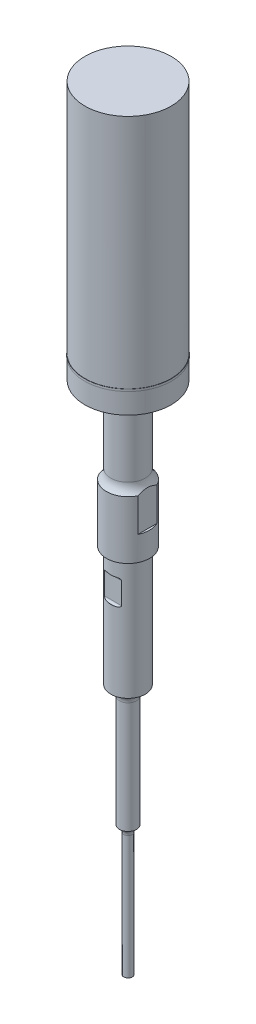
SolidWorks part; units mm, degrees
ref_plane "Front Plane" through (0, 0, 0) normal (0, 0, 1) x (1, 0, 0)
ref_plane "Top Plane" through (0, 0, 0) normal (0, 1, 0) x (1, 0, 0)
ref_plane "Right Plane" through (0, 0, 0) normal (1, 0, 0) x (0, 0, -1)
sketch "Sketch1" plane through (0, 0, 0) normal (0, 0, 1) x (1, 0, 0)
  line L0 (0, 0) -> (15.875, 0)
  line L1 (15.875, 0) -> (15.875, -95.25)
  line L2 (15.875, -95.25) -> (7.75, -95.25)
  line L3 (6.35, -99.25) -> (6.35, -123.35)
  line L5 (7.9375, -126.85) -> (7.9375, -148.15)
  line L6 (7.9375, -148.15) -> (6.35, -148.15)
  line L7 (6.35, -148.15) -> (6.35, -192.25)
  line L9 (3.15, -195.95) -> (3.15, -236.95)
  line L11 (1.6, -239.35) -> (1.6, -284.75)
  line L12 (1.6, -284.75) -> (0, -284.75)
  line L13 (0, -284.75) -> (0, 0)
  line L14 (-1.6, -239.35) -> (-1.6, -284.75) construction
  line L16 (-3.15, -195.95) -> (-3.15, -236.95) construction
  line L18 (-6.35, -148.15) -> (-6.35, -192.25) construction
  line L19 (-7.9375, -148.15) -> (-6.35, -148.15) construction
  line L20 (-7.9375, -126.85) -> (-7.9375, -148.15) construction
  line L22 (-6.35, -99.25) -> (-6.35, -123.35) construction
  line L23 (-15.875, -95.25) -> (-7.75, -95.25) construction
  line L24 (-15.875, 0) -> (-15.875, -95.25) construction
  arc A0 (6.35, -99.25) -> (7.75, -95.25) centre (12.7643, -99.25) cw
  arc A1 (-6.35, -99.25) -> (-7.75, -95.25) centre (-12.7643, -99.25) ccw construction
  arc A2 (6.35, -123.35) -> (7.9375, -126.85) centre (11.002, -123.35) ccw
  arc A3 (-6.35, -123.35) -> (-7.9375, -126.85) centre (-11.002, -123.35) cw construction
  arc A4 (1.6, -239.35) -> (3.15, -236.95) centre (4.2331, -239.35) cw
  arc A5 (-1.6, -239.35) -> (-3.15, -236.95) centre (-4.2331, -239.35) ccw construction
  arc A6 (3.15, -195.95) -> (6.35, -192.25) centre (6.8891, -195.95) cw
  arc A7 (-3.15, -195.95) -> (-6.35, -192.25) centre (-6.8891, -195.95) ccw construction
  dimension "D1" = 31.75
  dimension "D2" = 95.25
  dimension "D3" = 12.7
  dimension "D4" = 21.3
  dimension "D5" = 31.6
  dimension "D6" = 44.1
  dimension "D7" = 44.7
  dimension "D8" = 47.8
  dimension "D9" = 3.2
  dimension "D10" = 6.3
  dimension "D11" = 12.7
  dimension "D12" = 15.875
  dimension "D13" = 4
  dimension "D14" = 15.5
  dimension "D15" = 3.5
  dimension "D16" = 2.4
  dimension "D17" = 3.7
revolve "Revolve1" add sketch "Sketch1" angle 360 about L13
sketch "Sketch3" plane through (0, 0, 0) normal (0, 0, 1) x (1, 0, 0)
  line L0 (-7.9375, -126.85) -> (-7.9375, -148.15)
  line L1 (7.9375, -148.15) -> (7.9375, -126.85)
  line L2 (7.9375, -139.15) -> (7.9375, -126.85)
  line L3 (0, -17.4625) -> (0, 17.4625) construction
  line L4 (7.9375, -139.15) -> (7.1438, -139.15)
  line L5 (7.1438, -139.15) -> (7.1437, -125.949)
  line L6 (-7.1438, -139.15) -> (-7.1437, -125.949)
  line L7 (-7.9375, -139.15) -> (-7.1438, -139.15)
  line L8 (-7.9375, -139.15) -> (-7.9375, -126.85)
  arc A0 (-7.9375, -126.85) -> (-6.35, -123.35) centre (-11.002, -123.35) ccw
  arc A1 (6.35, -123.35) -> (7.9375, -126.85) centre (11.002, -123.35) ccw
  arc A2 (7.1437, -125.949) -> (7.9375, -126.85) centre (11.002, -123.35) ccw
  arc A4 (-7.1437, -125.949) -> (-7.9375, -126.85) centre (-11.002, -123.35) cw
  dimension "D1" = 9
  dimension "D2" = 14.2875
extrude "Cut-Extrude1" cut sketch "Sketch3" against normal through all both and the other way through all
sketch "Sketch4" plane through (0, 0, 0) normal (1, 0, 0) x (0, 0, -1)
  line L0 (-6.35, -148.15) -> (-6.35, -192.25)
  line L1 (6.35, -192.25) -> (6.35, -148.15)
  line L2 (6.35, -192.25) -> (6.35, -148.15) construction
  line L3 (0, 17.4625) -> (0, -17.4625) construction
  line L4 (6.35, -163.5805) -> (6.2245, -163.5805)
  line L5 (6.35, -163.5805) -> (6.35, -154.1825)
  line L6 (6.35, -154.1825) -> (6.2245, -154.1825)
  line L7 (5.5245, -162.8805) -> (5.5245, -154.8825)
  line L8 (-5.5245, -162.8805) -> (-5.5245, -154.8825)
  line L9 (-6.35, -154.1825) -> (-6.2245, -154.1825)
  line L10 (-6.35, -163.5805) -> (-6.35, -154.1825)
  line L11 (-6.35, -163.5805) -> (-6.2245, -163.5805)
  arc A0 (6.2245, -163.5805) -> (5.5245, -162.8805) centre (6.2245, -162.8805) cw
  arc A1 (5.5245, -154.8825) -> (6.2245, -154.1825) centre (6.2245, -154.8825) cw
  arc A2 (-5.5245, -154.8825) -> (-6.2245, -154.1825) centre (-6.2245, -154.8825) ccw
  arc A3 (-6.2245, -163.5805) -> (-5.5245, -162.8805) centre (-6.2245, -162.8805) ccw
  point P22 (-5.5245, -158.8815)
  dimension "D1" = 0.7
  dimension "D2" = 9.398
  dimension "D3" = 11.049
  dimension "D4" = 6.0325
extrude "Cut-Extrude2" cut sketch "Sketch4" against normal through all both and the other way through all
sketch "Sketch5" plane through (0, 0, 0) normal (0, 1, 0) x (1, 0, 0)
  line L1 (-4.3371, 7.5121) -> (-8.6742, 0)
  line L2 (-8.6742, 0) -> (-4.3371, -7.512)
  line L3 (-4.3371, -7.512) -> (4.3371, -7.512)
  line L4 (4.3371, -7.512) -> (8.6742, 0)
  line L5 (8.6742, 0) -> (4.3371, 7.512)
  line L6 (4.3371, 7.512) -> (-4.3371, 7.5121)
  circle A0 centre (0, 0) radius 7.512 construction
  dimension "D1" = 15.0241
extrude "Boss-Extrude1" [suppressed] add sketch "Sketch5" along normal blind 13.7
sketch "Sketch6" [suppressed] plane through (0, 0, 0) normal (0, 0, 1) x (1, 0, 0)
  line L0 (8.6742, 13.7) -> (-8.6742, 13.7)
  line L1 (7.35, 13.7) -> (0, 13.7)
  line L2 (0, 13.7) -> (0, 50.2)
  line L3 (0, 50.2) -> (5.65, 50.2)
  line L4 (5.65, 50.2) -> (7.35, 13.7)
  dimension "D1" = 5.65
  dimension "D2" = 7.35
  dimension "D3" = 36.5
revolve "Revolve2" [suppressed] add sketch "Sketch6" angle 360 about L2
sketch "Sketch7" plane through (0, 0, 0) normal (0, 0, 1) x (1, 0, 0)
  line L0 (15.875, -95.25) -> (15.875, 0) construction
  line L1 (15.875, -87.65) -> (15.975, -87.65)
  line L2 (15.875, -87.65) -> (15.875, -86.85)
  line L3 (15.875, -86.85) -> (15.975, -86.85)
  line L4 (15.975, -87.65) -> (15.975, -86.85)
  dimension "D1" = 7.6
  dimension "D2" = 0.8
  dimension "D3" = 0.1
revolve "Dont Clamp Below" add sketch "Sketch7" angle 360 about L13
